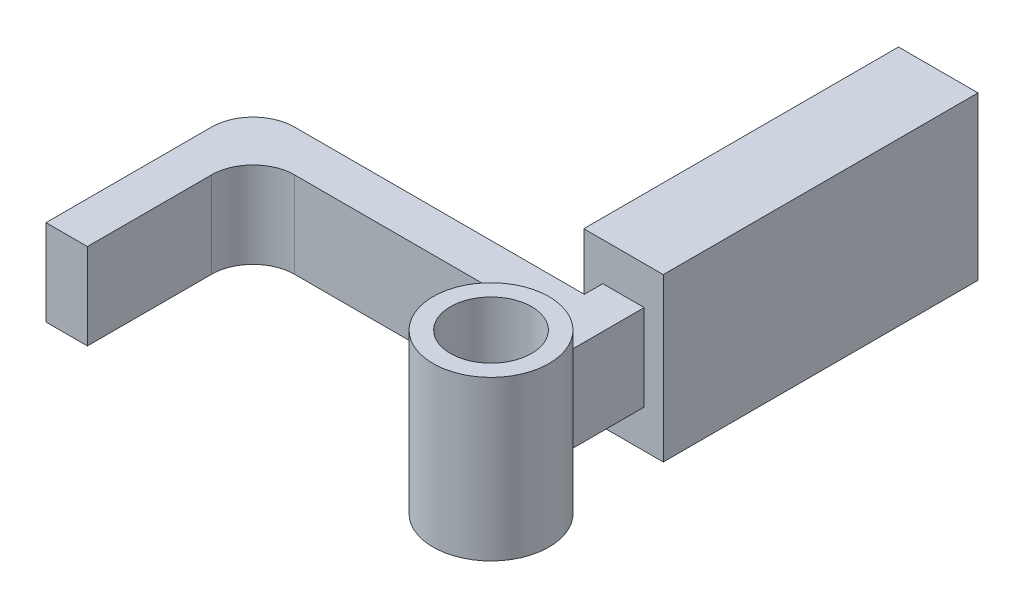
SolidWorks part; units mm, degrees
ref_plane "Front Plane" through (0, 0, 0) normal (0, 0, 1) x (1, 0, 0)
ref_plane "Top Plane" through (0, 0, 0) normal (0, 1, 0) x (1, 0, 0)
ref_plane "Right Plane" through (0, 0, 0) normal (1, 0, 0) x (0, 0, -1)
sketch "Sketch1" plane through (0, 0, 0) normal (0, 1, 0) x (1, 0, 0)
  line L2 (0, 0) -> (0, -4.1957) construction
  arc A1 (2.4164, -2.532) -> (-2.4164, -2.532) centre (0, 0) ccw
  circle A2 centre (0, 0) radius 2.45
  circle A3 centre (0, 0) radius 3.5
  dimension "D1" = 4.9
  dimension "D2" = 7
extrude "hole" add sketch "Sketch1" along normal blind 5.2 contours A2 A3 A1 region at (0, 0, 3.401)
sketch "Sketch2" plane through (0, 0, 0) normal (0, -1, 0) x (1, 0, 0)
  line L0 (0, 0) -> (0, -8) construction
  line L1 (0, -8) -> (0, -3.5) construction
  line L2 (0, -3.5) -> (0, -5.75) construction
  line L3 (-1.25, -8) -> (-1.25, -3.5)
  line L4 (-1.25, -8) -> (1.25, -8)
  line L5 (-1.25, -3.5) -> (1.25, -3.5)
  line L6 (1.25, -8) -> (1.25, -3.5)
  line L7 (-1.25, -8) -> (1.25, -3.5) construction
  line L8 (-1.25, -3.5) -> (1.25, -8) construction
  line L9 (-1.25, -3.5) -> (-1.25, -3.2692)
  line L10 (1.25, -3.5) -> (1.25, -3.2692)
  line L11 (1.25, -3.2692) -> (-1.25, -3.2692)
  circle A0 centre (0, 0) radius 3.5 construction
  circle M4 centre (0, 0) radius 3.5
  dimension "D1" = 8
  dimension "D2" = 4.5
  dimension "D3" = 2.25
  dimension "D4" = 2.5
  dimension "D5" = 4.5
extrude "Boss-Extrude2" add sketch "Sketch2" against normal blind 5.2 contours L4 L6 L5 L3 | L5 L10 M4 | L9 L5 M4 region at (0, 0, -5.75) region at (-0.9396, 0, -3.4312) region at (0.9396, 0, -3.4312)
sketch "Sketch3" plane through (0, 0, -8) normal (0, 0, -1) x (-1, 0, 0)
  line L0 (-1.25, 5.2) -> (1.25, 0) construction
  line L2 (-2.4, -2.3) -> (2.4, -2.3)
  line L3 (-2.4, -2.3) -> (-2.4, 7.5)
  line L4 (-2.4, 7.5) -> (2.4, 7.5)
  line L5 (2.4, -2.3) -> (2.4, 7.5)
  line L6 (-2.4, -2.3) -> (2.4, 7.5) construction
  line L7 (-2.4, 7.5) -> (2.4, -2.3) construction
  point P4 (0, 2.6)
  dimension "D1" = 4.8
  dimension "D2" = 9.8
extrude "Boss-Extrude3" add sketch "Sketch3" along normal blind 19
sketch "Sketch5" plane through (0, 0, 0) normal (0, -1, 0) x (1, 0, 0)
  line L0 (-1.25, -3.2692) -> (-1.25, -8) construction
  line L1 (-1.25, -5.6346) -> (-1.25, -6.8846) construction
  line L2 (-21.25, -6.8846) -> (-18.75, -4.3846) construction
  line L3 (-1.25, -6.8846) -> (-21.25, -6.8846)
  line L4 (-1.25, -6.8846) -> (-1.25, -4.3846)
  line L5 (-1.25, -4.3846) -> (-21.25, -4.3846)
  line L6 (-21.25, -6.8846) -> (-21.25, -4.3846)
  line L7 (-21.25, -6.8846) -> (-18.75, -6.8846)
  line L8 (-21.25, -6.8846) -> (-21.25, 5.6154)
  line L9 (-21.25, 5.6154) -> (-18.75, 5.6154)
  line L10 (-18.75, -6.8846) -> (-18.75, 5.6154)
  line L11 (-18.75, -4.3846) -> (-18.75, -1.8846) construction
  line L12 (-18.75, -1.8846) -> (-16.25, -1.8846) construction
  arc A0 (-18.75, -1.8846) -> (-16.25, -4.3846) centre (-16.25, -1.8846) ccw
  arc A1 (-21.25, -4.3846) -> (-18.75, -6.8846) centre (-18.75, -4.3846) ccw
  line M10 (-1.25, -3.2692) -> (-1.25, -8)
  dimension "D8" = 2.5
  dimension "D9" = 2.5
  dimension "D1" = 1.25
  dimension "D2" = 2.5
  dimension "D3" = 20
  dimension "D4" = 2.5
  dimension "D5" = 12.5
  dimension "D6" = 2.5
  dimension "D7" = 2.5
extrude "lever arm" add sketch "Sketch5" against normal up to surface (5.2 mm away) contours L10 L3 L5 M10 | L5 A1 L10 | A0 L10 L5 | L5 L10 L9 L8 region at (-10, 0, -5.6346) region at (-19.811, 0, -5.4456) region at (-18.1916, 0, -3.8262) region at (-20, 0, 0.6154) up to face at (0, 5.2, -3.9423)
sketch "Sketch6" plane through (0, 0, 0) normal (0, -1, 0) x (1, 0, 0)
  circle A0 centre (0, 0) radius 2.45
  circle A1 centre (0, 0) radius 3.5
  dimension "D1" = 4.9
  dimension "D2" = 7
extrude "Boss-Extrude4" add sketch "Sketch6" along normal blind 2.2 and the other way blind 7.4
scale "Scale1" scale about centroid uniform scaling yes scale factor 0.8
